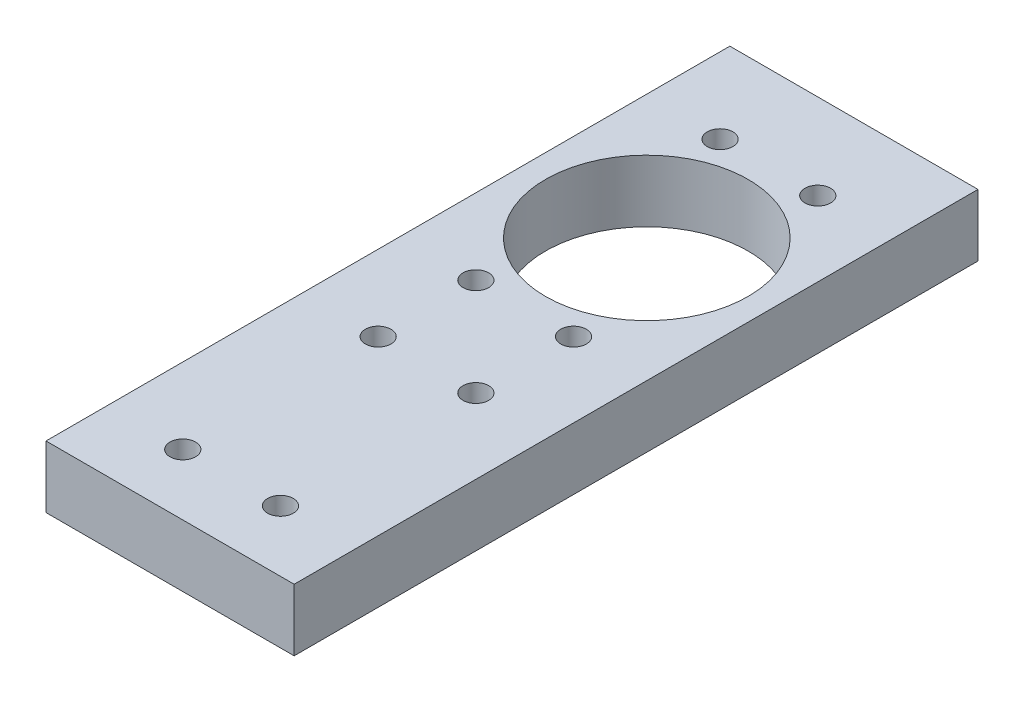
SolidWorks part; units mm, degrees
ref_plane "Front Plane" through (0, 0, 0) normal (0, 0, 1) x (1, 0, 0)
ref_plane "Top Plane" through (0, 0, 0) normal (0, 1, 0) x (1, 0, 0)
ref_plane "Right Plane" through (0, 0, 0) normal (1, 0, 0) x (0, 0, -1)
sketch "Sketch2" plane through (0, 0, 0) normal (0, 1, 0) x (1, 0, 0)
  line L1 (0, 0) -> (101.6, 0)
  line L2 (0, 0) -> (0, 280)
  line L3 (0, 280) -> (101.6, 280)
  line L4 (101.6, 0) -> (101.6, 280)
  dimension "D1" = 101.6
  dimension "D2" = 280
extrude "Boss-Extrude1" add sketch "Sketch2" along normal blind 25.4
sketch "Sketch3" plane through (0, 25.4, 0) normal (0, 1, 0) x (1, 0, 0)
  line L1 (0, 280) -> (51, 280)
  line L2 (0, 280) -> (0, 195)
  line L3 (0, 195) -> (51, 195)
  line L4 (51, 280) -> (51, 195)
  line L5 (31, 245) -> (71, 245)
  line L6 (31, 245) -> (31, 145)
  line L7 (31, 145) -> (71, 145)
  line L8 (71, 245) -> (71, 145)
  line L9 (31, 245) -> (71, 145) construction
  line L10 (31, 145) -> (71, 245) construction
  circle A0 centre (71, 245) radius 5.25
  circle A1 centre (31, 245) radius 5.25
  circle A2 centre (71, 145) radius 5.25
  circle A3 centre (31, 145) radius 5.25
  circle A4 centre (51, 195) radius 41.5
  dimension "D1" = 51
  dimension "D2" = 85
  dimension "D3" = 40
  dimension "D4" = 100
extrude "Cut-Extrude1" cut sketch "Sketch3" against normal blind 25.4 contours A1 | A0 | A4 | A2 | A3
sketch "Sketch4" plane through (0, 25.4, 0) normal (0, 1, 0) x (1, 0, 0)
  line L1 (0, 280) -> (51, 280)
  line L2 (0, 280) -> (0, 65)
  line L3 (0, 65) -> (51, 65)
  line L4 (51, 280) -> (51, 65)
  line L5 (31, 25) -> (71, 25)
  line L6 (31, 25) -> (31, 105)
  line L7 (31, 105) -> (71, 105)
  line L8 (71, 25) -> (71, 105)
  line L9 (31, 25) -> (71, 105) construction
  line L10 (31, 105) -> (71, 25) construction
  circle A0 centre (71, 105) radius 5.25
  circle A1 centre (31, 105) radius 5.25
  circle A2 centre (31, 25) radius 5.25
  circle A3 centre (71, 25) radius 5.25
  dimension "D1" = 51
  dimension "D2" = 215
  dimension "D3" = 40
  dimension "D4" = 80
extrude "Cut-Extrude2" cut sketch "Sketch4" against normal blind 25.4 contours A1 | A0 | A3 | A2
